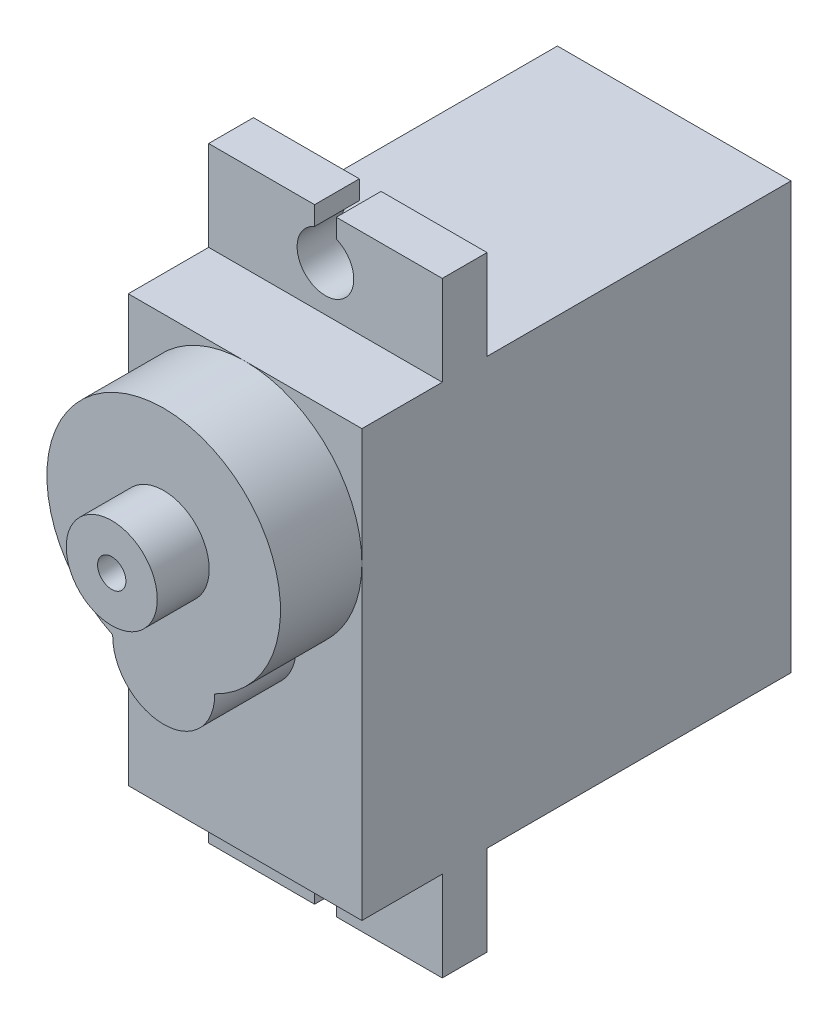
SolidWorks part; units mm, degrees
note: '?' marks a value the reader was unsure of.
ref_plane "Front Plane" through (0, 0, 0) normal (0, 0, 1) x (1, 0, 0)
ref_plane "Top Plane" through (0, 0, 0) normal (0, 1, 0) x (1, 0, 0)
ref_plane "Right Plane" through (0, 0, 0) normal (1, 0, 0) x (0, 0, -1)
sketch "Sketch1" plane through (0, 0, 0) normal (0, 0, 1) x (1, 0, 0)
  line L1 (-6.1849, -11.2776) -> (6.1849, -11.2776)
  line L2 (-6.1849, -11.2776) -> (-6.1849, 11.2776)
  line L3 (-6.1849, 11.2776) -> (6.1849, 11.2776)
  line L4 (6.1849, -11.2776) -> (6.1849, 11.2776)
  line L5 (-6.1849, -11.2776) -> (6.1849, 11.2776) construction
  line L6 (-6.1849, 11.2776) -> (6.1849, -11.2776) construction
  point P0 (0, 0)
  dimension "D1" = 12.3698
  dimension "D2" = 22.5552
extrude "Boss-Extrude1" add sketch "Sketch1" along normal mid plane 22.7203
ref_plane "Plane1" through (0, 0, 7.1056) normal (0, 0, 1) x (1, 0, 0)
sketch "Sketch2" plane through (0, 0, 7.1056) normal (0, 0, 1) x (1, 0, 0)
  line L0 (-0.575, 16.0401) -> (-6.1849, 16.0401)
  line L1 (-6.1849, 16.0401) -> (-6.1849, 11.2776)
  line L2 (-6.1849, 11.2776) -> (6.1849, 11.2776)
  line L3 (6.1849, 11.2776) -> (6.1849, 16.0401)
  line L4 (6.1849, 16.0401) -> (0.575, 16.0401)
  line L5 (0.575, 16.0401) -> (0.575, 15.0401)
  line L6 (-0.575, 15.0401) -> (-0.575, 16.0401)
  line L7 (-1.5, 13.6547) -> (1.5, 13.6547) construction
  arc A0 (0.575, 15.0401) -> (-0.575, 15.0401) centre (0, 13.6547) cw
  dimension "D2" = 3
  dimension "D1" = 4.7625
  dimension "D3" = 1
  dimension "D4" = 1.15
extrude "Boss-Extrude2" add sketch "Sketch2" against normal blind 2.37
mirror "Mirror1" about plane through (0, 0, 0) normal (0, 1, 0) of "Boss-Extrude2"
sketch "Sketch3" plane through (0, 0, 11.3601) normal (0, 0, 1) x (1, 0, 0)
  line L0 (6.1849, 11.2776) -> (-6.1849, 11.2776) construction
  line L1 (6.1849, -11.2776) -> (6.1849, 11.2776) construction
  line L2 (2.7, -0.5224) -> (2.7, -0.4717)
  line L3 (-2.7, -0.5224) -> (-2.7, -0.4717)
  line L4 (0, 11.2776) -> (0, -3.2224) construction
  arc A0 (2.7, -0.4717) -> (-2.7, -0.4717) centre (0, 5.0927) ccw
  arc A1 (2.7, -0.5224) -> (-2.7, -0.5224) centre (0, -0.5224) cw
  dimension "D1" = 5.4
  dimension "D2" = 14.5
extrude "Boss-Extrude3" add sketch "Sketch3" along normal blind 4.31
sketch "Sketch4" plane through (0, 0, 15.6702) normal (0, 0, 1) x (1, 0, 0)
  circle A0 centre (0, 5.0927) radius 2.41
  circle A1 centre (0, 5.0927) radius 0.75
  dimension "D1" = 4.82
  dimension "D2" = 1.5
extrude "Boss-Extrude4" add sketch "Sketch4" along normal blind 2.75
ref_axis "Axis1" through (0, 5.0927, 22.3459) along (0, 0, -1)?
